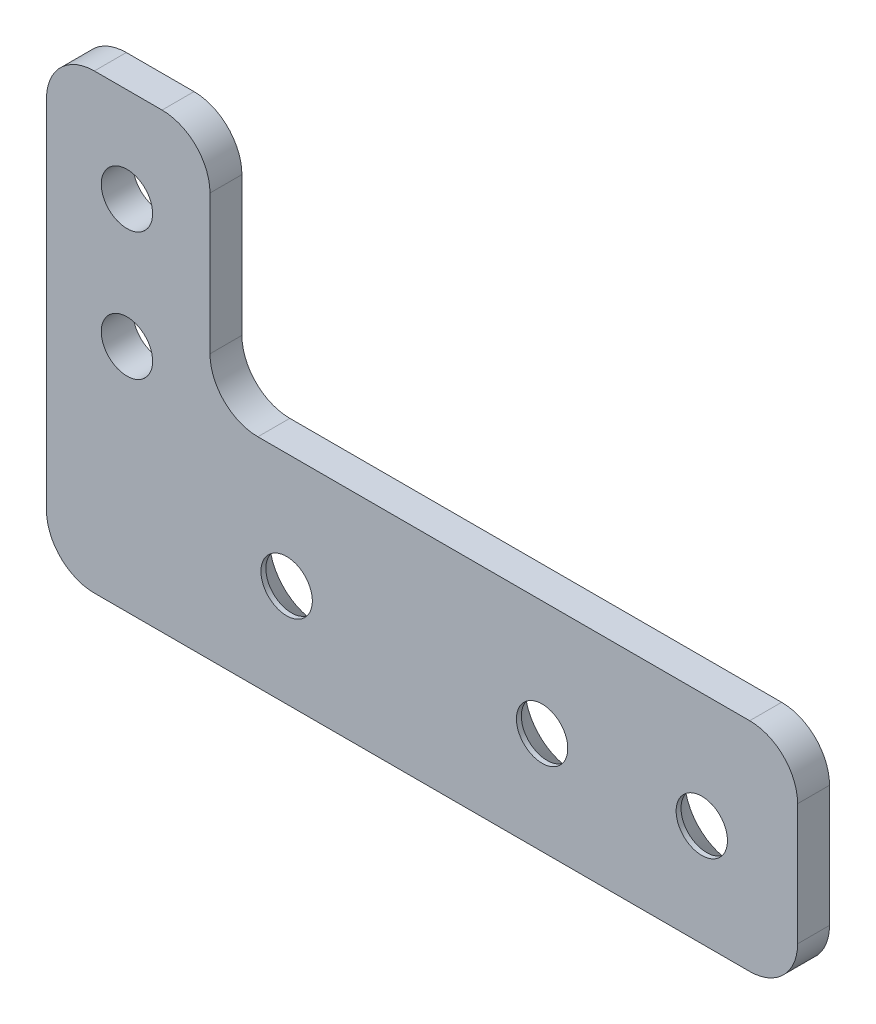
SolidWorks part; units mm, degrees
material "6061-T6 (SS)"
ref_plane "Front Plane" through (0, 0, 0) normal (0, 0, 1) x (1, 0, 0)
ref_plane "Top Plane" through (0, 0, 0) normal (0, 1, 0) x (1, 0, 0)
ref_plane "Right Plane" through (0, 0, 0) normal (1, 0, 0) x (0, 0, -1)
sketch "Sketch1" plane through (0, 0, 0) normal (0, 0, 1) x (1, 0, 0)
  line L0 (41.275, -11.049) -> (-33.401, -11.049) construction
  line L1 (-41.275, -23.749) -> (41.275, -23.749)
  line L2 (-41.275, -23.749) -> (-41.275, 23.749)
  line L3 (-41.275, 23.749) -> (41.275, 23.749)
  line L4 (41.275, -23.749) -> (41.275, 23.749)
  line L5 (-41.275, -23.749) -> (41.275, 23.749) construction
  line L6 (-41.275, 23.749) -> (41.275, -23.749) construction
  line L7 (41.275, 23.749) -> (-17.145, 23.749)
  line L8 (41.275, 23.749) -> (41.275, 0.381)
  line L9 (41.275, 0.381) -> (-17.145, 0.381)
  line L10 (-17.145, 23.749) -> (-17.145, 0.381)
  line L11 (-41.275, -23.749) -> (-33.401, -23.749)
  line L12 (-41.275, -23.749) -> (-41.275, 23.749)
  line L13 (-41.275, 23.749) -> (-33.401, 23.749)
  line L14 (-33.401, -23.749) -> (-33.401, 23.749)
  line L15 (-33.401, -23.749) -> (41.275, -23.749)
  line L16 (-33.401, -23.749) -> (-33.401, -21.209)
  line L17 (-33.401, -21.209) -> (41.275, -21.209)
  line L18 (41.275, -23.749) -> (41.275, -21.209)
  line L19 (-33.401, 23.876) -> (-17.145, 23.876) construction
  circle A0 centre (-25.4, -11.049) radius 2.5527
  circle A1 centre (-25.4, 1.651) radius 2.5527
  circle A2 centre (-25.4, 14.351) radius 2.5527
  point P0 (0, 0)
  point P22 (31.75, -11.049)
  point P23 (-9.525, -11.049)
  point P24 (15.875, -11.049)
  dimension "D7" = 5.1054
  dimension "D1" = 82.55
  dimension "D2" = 47.498
  dimension "D3" = 24.13
  dimension "D4" = 24.13
  dimension "D5" = 7.874
  dimension "D6" = 47.498
  dimension "D8" = 15.875
  dimension "D9" = 12.7
  dimension "D10" = 12.7
  dimension "D11" = 12.7
  dimension "D12" = 9.525
  dimension "D13" = 57.15
  dimension "D14" = 15.875
  dimension "D15" = 15.875
  dimension "D16" = 2.54
extrude "Boss-Extrude1" add sketch "Sketch1" along normal blind 3.175 contours L14 L17 L4 L9 L10 L3 A2 A1 A0 | A0 region at (-0.8769, -6.375, 0) region at (-25.4, -11.049, 0)
fillet "Fillet1" radius 4.7625 6 edges at (-33.401, 23.749, 1.5875) (-17.145, 23.749, 1.5875) (-17.145, 0.381, 1.5875) (41.275, 0.381, 1.5875) (41.275, -21.209, 1.5875) (-33.401, -21.209, 1.5875)
hole_wizard "CSK for #10 Flat Head Machine Screw3" positions "Sketch6" profile "Sketch7" countersink size "#10" standard "ANSI Inch" end condition through all
sketch "Sketch6" plane through (0, 0, 0) normal (0, 0, -1) x (-1, 0, 0)
  point P0 (-31.75, -11.049)
  point P3 (-15.875, -11.049)
  point P6 (9.525, -11.049)
sketch "Sketch7" plane through (31.75, -11.049, 0) normal (1, 0, 0) x (0, 1, 0)
  line L0 (0, 0) -> (0, 3.175)
  line L1 (0, 3.175) -> (2.5527, 3.175)
  line L2 (2.5527, 3.175) -> (2.5527, 2.6882)
  line L3 (2.5527, 2.6882) -> (4.8895, 0)
  line L5 (4.8895, 0) -> (0, 0)
  line L6 (-2.5527, 2.6882) -> (-4.8895, 0) construction
  line L11 (0, -6.35) -> (0, 107.95) construction
  dimension "Thru Hole Dia." = 5.1054
  dimension "Thru Hole Depth" = 3.175
  dimension "Near C'Sink Dia." = 9.779
  dimension "Near C'Sink Angle" = 82
